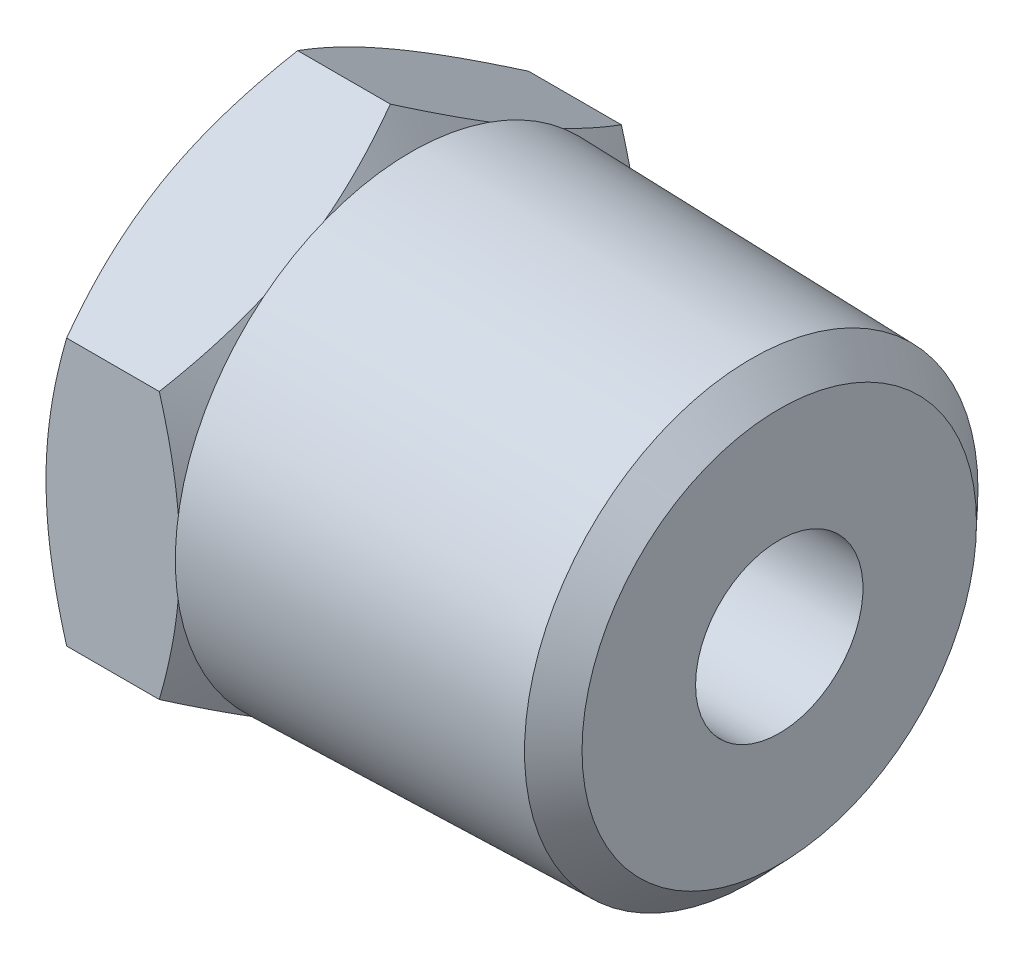
SolidWorks part; units mm, degrees
ref_plane "Front Plane" through (0, 0, 0) normal (0, 0, 1) x (1, 0, 0)
ref_plane "Top Plane" through (0, 0, 0) normal (0, 1, 0) x (1, 0, 0)
ref_plane "Right Plane" through (0, 0, 0) normal (1, 0, 0) x (0, 0, -1)
sketch "Sketch1" plane through (0, 0, 0) normal (0, 0, 1) x (1, 0, 0)
  line L0 (-9.525, 0) -> (9.525, 0) construction
  line L1 (-9.525, 8.763) -> (-9.525, -8.763) construction
  line L2 (9.525, 8.5725) -> (9.525, -8.5725) construction
  line L3 (-4.445, 6.858) -> (-4.445, -6.858) construction
  line L4 (9.525, -8.5725) -> (-9.525, -9.0713) construction
  point P7 (-5.7302, 0)
  point P8 (-4.445, 0)
  point P11 (3.8806, -8.7203)
  dimension "Male Pipe OD" = 17.145
  dimension "Hex" = 17.526
  dimension "Male TE" = 15.2552
  dimension "Female TE" = 5.08
  dimension "A" = 19.05
  dimension "Female Pipe OD" = 13.716
  dimension "D1" = 1.5
  dimension "D2" = 5.6444
ref_plane "Plane1" through (9.525, 0, 0) normal (1, 0, 0) x (0, 0, -1)
sketch "Sketch2" plane through (9.525, 0, 0) normal (1, 0, 0) x (0, 0, -1)
  circle A0 centre (0, 0) radius 8.5725
extrude "Extrude1" add sketch "Sketch2" against normal up to vertex (13.97 mm away) draft 1.5 up to point (-4.445, 0, 0) draft outward yes
sketch "Sketch3" plane through (9.525, 0, 0) normal (1, 0, 0) x (0, 0, -1)
  circle A0 centre (0, 0) radius 8.5725 construction
  circle A1 centre (0, 0) radius 8.5725
curve "Helix/Spiral1" parameters "Male pitch"=1.4111
chamfer "Chamfer1" distance 1.0626 angle 45 1 edges at (9.525, 0, -8.5725) first distance on face at (-4.445, 0, -8.9383)
sketch "Sketch4" plane through (0, 0, 0) normal (0, 0, 1) x (1, 0, 0)
  line L0 (8.9076, 8.5725) -> (9.4368, 7.656)
  line L1 (9.4368, 7.656) -> (9.6132, 7.656)
  line L2 (9.6132, 7.656) -> (10.1424, 8.5725)
  line L3 (8.9076, 8.5725) -> (10.1424, 8.5725) construction
  line L4 (9.525, 7.656) -> (9.525, 8.5725) construction
  line L5 (9.1722, 8.1142) -> (9.8778, 8.1142) construction
  line L6 (10.1424, 8.5725) -> (8.7677, 8.8149)
  line L7 (8.9076, 8.5725) -> (8.7677, 8.8149)
  dimension "D1" = 10
  dimension "D2" = 60
  dimension "D3" = 0.1764
  dimension "D4" = 0.7056
sweep "Cut-Sweep1" [suppressed] cut profiles "Sketch4" path "Helix/Spiral1"
sketch "Sketch5" plane through (-4.445, 0, 0) normal (-1, 0, 0) x (0, 0, 1)
  line L1 (0, 10.1186) -> (-8.763, 5.0593)
  line L2 (-8.763, 5.0593) -> (-8.763, -5.0593)
  line L3 (-8.763, -5.0593) -> (0, -10.1186)
  line L4 (0, -10.1186) -> (8.763, -5.0593)
  line L5 (8.763, -5.0593) -> (8.763, 5.0593)
  line L6 (8.763, 5.0593) -> (0, 10.1186)
  circle A0 centre (0, 0) radius 8.763 construction
  dimension "D1" = 17.526
extrude "Extrude2" add sketch "Sketch5" along normal up to vertex (5.08 mm away) up to point (-9.525, 0, 0)
ref_plane "Plane2" through (-4.445, 0, 0) normal (1, 0, 0) x (0, 0, -1)
sketch "Sketch6" plane through (-4.445, 0, 0) normal (1, 0, 0) x (0, 0, -1)
  circle A0 centre (0, 0) radius 6.858
extrude "Cut-Extrude1" [suppressed] cut sketch "Sketch6" against normal through all draft 1.5 draft outward yes
sketch "Sketch7" [suppressed] plane through (-4.445, 0, 0) normal (-1, 0, 0) x (0, 0, 1)
  circle A1 centre (0, 0) radius 6.858
  circle A2 centre (0, 0) radius 6.858
  dimension "D1" = 0
curve "Helix/Spiral2" [suppressed] parameters "Female Pitch"=1.4111
sketch "Sketch9" [suppressed] plane through (-9.525, 0, 0) normal (-1, 0, 0) x (0, 0, 1)
  circle A0 centre (0, 0) radius 6.991 construction
  circle A1 centre (0, 0) radius 6.991
sketch "Sketch8" plane through (0, 0, 0) normal (0, 0, 1) x (1, 0, 0)
  line L0 (-5.0624, 6.858) -> (-3.8276, 6.858) construction
  line L1 (-3.8276, 6.858) -> (-4.3568, 5.9415)
  line L2 (-4.3568, 5.9415) -> (-4.5332, 5.9415)
  line L3 (-4.5332, 5.9415) -> (-5.0624, 6.858)
  line L4 (-3.8276, 6.858) -> (-5.2023, 7.1004)
  line L5 (-5.0624, 6.858) -> (-5.2023, 7.1004)
  line L6 (-4.445, 5.9415) -> (-4.445, 6.858) construction
  line L7 (-4.7978, 6.3997) -> (-4.0922, 6.3997) construction
  dimension "D1" = 10
  dimension "D2" = 60
  dimension "D3" = 0.1764
  dimension "D4" = 0.7056
sweep "Sweep1" [suppressed] add profiles "Sketch8" path "Helix/Spiral2"
sketch "Sketch10" plane through (-9.525, 0, 0) normal (-1, 0, 0) x (0, 0, 1)
  line L3 (8.763, 5.0593) -> (0, 10.1186)
  line L4 (8.763, 5.0593) -> (0, 10.1186)
  line L5 (0, 10.1186) -> (-8.763, 5.0593)
  line L6 (0, 10.1186) -> (-8.763, 5.0593)
  line L10 (0, -10.1186) -> (8.763, -5.0593)
  line L11 (-8.763, 5.0593) -> (-8.763, -5.0593)
  line L12 (-8.763, 5.0593) -> (-8.763, -5.0593)
  line L13 (-8.763, -5.0593) -> (0, -10.1186)
  line L14 (-8.763, -5.0593) -> (0, -10.1186)
  line L15 (8.763, -5.0593) -> (8.763, 5.0593)
  line L16 (0, -10.1186) -> (8.763, -5.0593)
  line L17 (8.763, -5.0593) -> (8.763, 5.0593)
  dimension "D1" = 0
extrude "Cut-Extrude3" [suppressed] cut sketch "Sketch10" along normal through all
extrude "Cut-Extrude4" [suppressed] cut sketch "Sketch9" against normal through all draft 45
sketch "Sketch11" [suppressed] plane through (-4.445, 0, 0) normal (-1, 0, 0) x (0, 0, 1)
  circle A0 centre (0, 0) radius 5.9415
extrude "Cut-Extrude5" [suppressed] cut sketch "Sketch11" against normal through all
sketch "Sketch12" plane through (-9.525, 0, 0) normal (-1, 0, 0) x (0, 0, 1)
  circle A0 centre (0, 0) radius 8.763 construction
  circle A1 centre (0, 0) radius 8.763
extrude "Cut-Extrude6" cut sketch "Sketch12" against normal through all draft 60 flip side to cut
sketch "Sketch13" plane through (-4.445, 0, 0) normal (1, 0, 0) x (0, 0, -1)
  circle A1 centre (0, 0) radius 8.763
  circle A2 centre (0, 0) radius 8.763
  dimension "D1" = 0
extrude "Cut-Extrude7" cut sketch "Sketch13" against normal through all draft 60 flip side to cut
sketch "Sketch14" [suppressed] plane through (-9.525, 0, 0) normal (1, 0, 0) x (0, 0, -1)
  line L0 (0, 0) -> (4.2012, 4.2012) construction
  line L1 (0, 0) -> (5.9415, 0) construction
  circle A0 centre (0, 0) radius 5.9415 construction
  dimension "D1" = 45
sketch "Sketch16" plane through (-9.525, 0, 0) normal (-1, 0, 0) x (0, 0, 1)
  circle A0 centre (0, 0) radius 3.175
  dimension "D1" = 6.35
extrude "Cut-Extrude8" cut sketch "Sketch16" against normal through all
equation "\"D3@Sketch4\" = \"Male pitch@Helix/Spiral1\"*.125"
equation "\"D4@Sketch4\" = \"Male pitch@Helix/Spiral1\"*.50"
equation "\"D1@Chamfer1\" = \"Male pitch@Helix/Spiral1\"*.753"
equation "\"D1@Sketch5\" = \"Hex@Sketch1\""
equation "\"D3@Sketch8\" = \"Female Pitch@Helix/Spiral2\"*.125"
equation "\"D4@Sketch8\" = \"Female Pitch@Helix/Spiral2\"*.5"
equation "\"D2@Sketch1\" = \"Male pitch@Helix/Spiral1\"*4.0"
